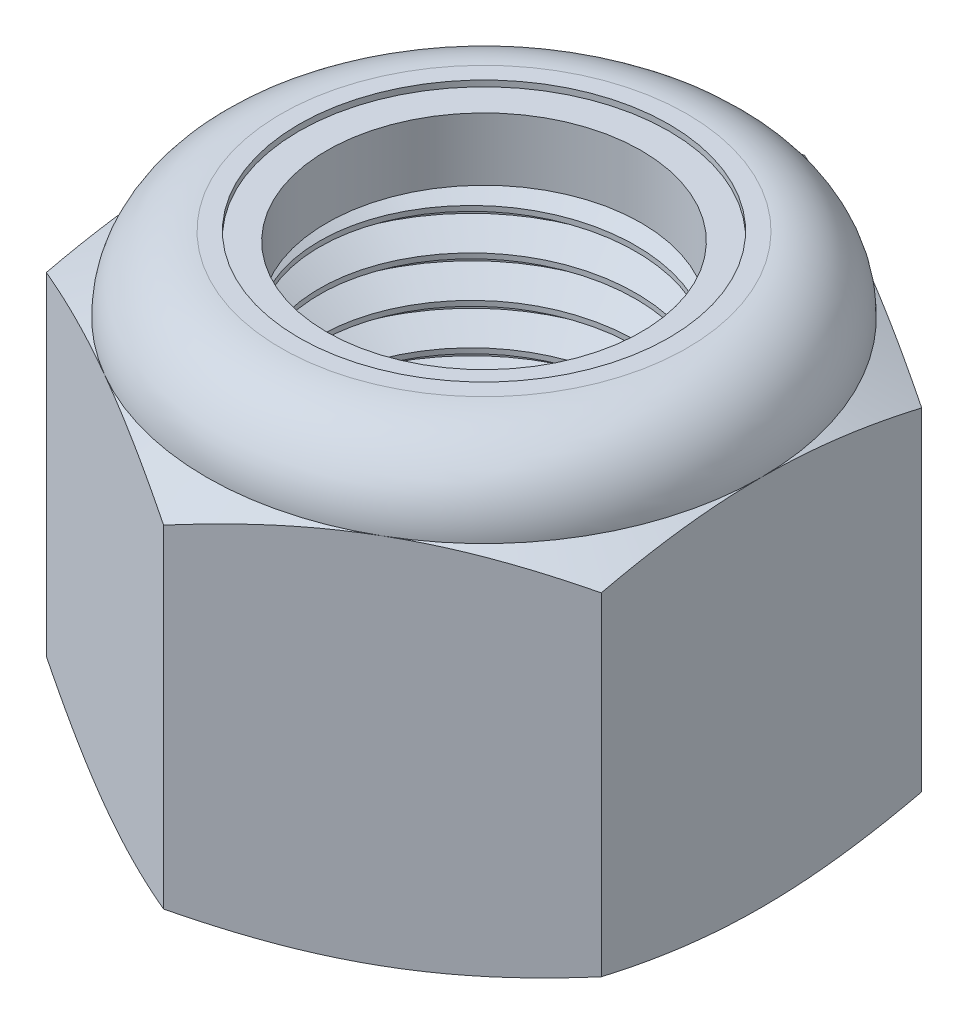
SolidWorks part; units mm, degrees
note: '?' marks a value the reader was unsure of.
ref_plane "Front" through (0, 0, 0) normal (0, 0, 1) x (1, 0, 0)
ref_plane "Top" through (0, 0, 0) normal (0, 1, 0) x (1, 0, 0)
ref_plane "Right" through (0, 0, 0) normal (1, 0, 0) x (0, 0, -1)
sketch "Sketch8" plane through (0, 0, 0) normal (1, 0, 0) x (0, 0, -1)
  line L0 (0, 0) -> (0, 11.5094) construction
  line L1 (7.1437, 0) -> (-7.1437, 0) construction
  line L2 (-4.7625, 11.5094) -> (4.7625, 11.5094) construction
  line L3 (4.7625, 11.5094) -> (4.7625, 10.451) construction
sketch "Sketch1" plane through (0, 0, 0) normal (0, 1, 0) x (1, 0, 0)
  line L1 (0, 8.2489) -> (-7.1438, 4.1244)
  line L2 (-7.1438, 4.1244) -> (-7.1437, -4.1244)
  line L3 (-7.1437, -4.1244) -> (0, -8.2489)
  line L4 (0, -8.2489) -> (7.1438, -4.1244)
  line L5 (7.1438, -4.1244) -> (7.1438, 4.1244)
  line L6 (7.1438, 4.1244) -> (0, 8.2489)
  circle A0 centre (0, 0) radius 7.1438 construction
  circle A1 centre (0, 0) radius 4.7625
extrude "Extrude1" add sketch "Sketch1" along normal up to vertex (11.5094 mm away) up to point (0, 11.5094, 0)
sketch "Sketch5" plane through (0, 0, 0) normal (1, 0, 0) x (0, 0, -1)
  line L0 (0, 0) -> (7.1437, 0)
  line L1 (7.1437, 0) -> (8.2489, 0.5153)
  line L2 (8.2489, 0.5153) -> (8.2489, 9.0758)
  line L3 (8.2489, 9.0758) -> (7.1437, 9.5911)
  line L4 (5.2255, 11.5094) -> (5.2255, 12.7794)
  line L5 (5.2255, 12.7794) -> (9.5189, 12.7794)
  line L6 (9.5189, 12.7794) -> (9.5189, -1.27)
  line L7 (9.5189, -1.27) -> (0, -1.27)
  line L8 (0, -1.27) -> (0, 0)
  line L9 (7.1437, 9.5911) -> (7.1437, 0) construction
  line L12 (8.2489, 11.5094) -> (8.2489, 0) construction
  line L13 (8.2489, 5.7547) -> (9.5189, 5.7547) construction
  line L15 (0, 0) -> (0, 12.7794) construction
  line L18 (7.1437, 0) -> (-7.1437, 0) construction
  line L19 (4.1244, 11.5094) -> (8.2489, 11.5094) construction
  line L20 (0, 12.7794) -> (5.2255, 12.7794) construction
  line L21 (4.1244, 0) -> (8.2489, 0) construction
  arc A0 (7.1437, 9.5911) -> (5.2255, 11.5094) centre (5.2255, 9.5911) ccw
  dimension "D1" = 25
  dimension "D2" = 1.27
  dimension "D4" = 1.9182
revolve "Cut-Revolve3" cut sketch "Sketch5" angle 360 about L15
sketch "Sketch4" plane through (0, 0, 0) normal (1, 0, 0) x (0, 0, -1)
  line L0 (0, 9.5911) -> (5.2388, 9.5911)
  line L1 (5.2388, 9.5911) -> (0, 7.1483)
  line L3 (0, 2.4429) -> (5.2388, 0)
  line L4 (5.2388, 0) -> (0, 0)
  line L5 (0, 0) -> (0, 9.5911) construction
  line L10 (0, 0) -> (0, 11.5094) construction
  line L11 (0, 2.4429) -> (0, 0)
  line L12 (0, 9.5911) -> (0, 7.1483)
  line L13 (6.1867, 9.5911) -> (0, 9.5911) construction
  dimension "D1" = 25
  dimension "D2" = 10.4775
sketch "Sketch6" plane through (0, 0, 0) normal (1, 0, 0) x (0, 0, -1)
  line L0 (0, 9.5911) -> (6.9913, 9.5911)
  line L1 (5.2255, 11.357) -> (2.6128, 11.357)
  line L2 (0, 12.7794) -> (0, 9.5911)
  line L3 (2.6128, 12.7794) -> (0, 12.7794)
  line L4 (0, 12.7794) -> (5.2255, 12.7794) construction
  line L5 (0, 0) -> (0, 12.7794) construction
  line L6 (0, 12.7794) -> (0, 0) construction
  line L7 (2.6128, 11.357) -> (2.6128, 12.7794)
  line L8 (5.2255, 11.5094) -> (5.2255, 11.357) construction
  line L9 (2.6128, 11.357) -> (0, 11.357) construction
  line L10 (0, 11.357) -> (0, 7.1483) construction
  arc A0 (6.9913, 9.5911) -> (5.2255, 11.357) centre (5.2255, 9.5911) ccw
  arc A1 (7.1437, 9.5911) -> (5.2255, 11.5094) centre (5.2255, 9.5911) ccw construction
  dimension "D1" = 0.1524
revolve "Cut-Revolve4" cut sketch "Sketch6" angle 360 about L6
revolve "Cut-Revolve2" cut sketch "Sketch4" angle 360 about L5
sketch "Sketch7" plane through (0, 0, 0) normal (1, 0, 0) x (0, 0, -1)
  line L0 (4.0481, 9.6673) -> (6.9134, 9.6673)
  line L1 (5.2255, 11.2808) -> (4.0481, 11.2808)
  line L2 (4.0481, 11.2808) -> (4.0481, 9.6673)
  line L3 (4.0481, 9.6673) -> (0, 9.6673) construction
  line L4 (0, 9.6673) -> (0, 11.2808) construction
  line L5 (0, 11.2808) -> (4.0481, 11.2808) construction
  line L6 (4.0481, 9.6673) -> (4.0481, 9.5911) construction
  line L7 (0, 9.5911) -> (6.9913, 9.5911) construction
  line L8 (5.2255, 11.2808) -> (5.2255, 11.357) construction
  arc A0 (6.9134, 9.6673) -> (5.2255, 11.2808) centre (5.2255, 9.5911) ccw
  arc A2 (6.9913, 9.5911) -> (5.2255, 11.357) centre (5.2255, 9.5911) ccw construction
  dimension "D1" = 0.0762
  dimension "D2" = 8.0963
revolve "Revolve2" add sketch "Sketch7" angle 360 about L4
sketch "Sketch2" plane through (0, 0, 0) normal (1, 0, 0) x (0, 0, -1)
  line L0 (-4.7625, 0) -> (-4.7625, 9.5911) construction
  line L1 (0, 0) -> (4.7625, 0)
  line L2 (0, 0) -> (0, 9.5911)
  line L3 (0, 9.5911) -> (4.7625, 9.5911)
  line L4 (4.7625, 0) -> (4.7625, 9.5911)
  line L6 (6.1867, 9.5911) -> (7.1437, 9.5911) construction
  line L7 (0, -4.7625) -> (0, 0) construction
revolve "Revolve1" add sketch "Sketch2" angle 360 about L7
sketch "Sketch9" plane through (0, 0, 0) normal (1, 0, 0) x (0, 0, -1)
  line L0 (4.8771, 10.5833) -> (4.8771, 9.525) construction
  line L1 (4.8771, 9.525) -> (3.9605, 10.0542) construction
  line L2 (3.9605, 10.0542) -> (4.8771, 10.5833) construction
  line L3 (4.0751, 10.1203) -> (4.0751, 9.988) construction
  line L4 (4.7625, 10.5172) -> (4.7625, 9.5911) construction
  line L5 (3.9605, 10.0542) -> (4.0751, 10.0542) construction
  line L6 (4.7625, 10.0542) -> (4.8771, 10.0542) construction
  line L7 (4.8198, 10.0542) -> (4.8198, 10.5503) construction
  line L8 (4.8771, 9.525) -> (4.8198, 10.5503)
  line L9 (4.8198, 10.5503) -> (4.0751, 10.1203)
  line L10 (4.0751, 10.1203) -> (4.0751, 9.988)
  line L11 (4.0751, 9.988) -> (4.8771, 9.525)
  dimension "D1" = 1.0583
  dimension "D2" = 0.1323
sketch "Sketch10" plane through (0, 9.5911, 0) normal (0, 1, 0) x (1, 0, 0)
  circle A1 centre (0, 0) radius 4.7625
  circle A2 centre (0, 0) radius 4.7625
  dimension "D1" = 0
curve "Helix/Spiral1" pitch 1.0583 height 12.5677 turns 11.875
sweep "Cut-Sweep1" cut profiles "Sketch9" path "Helix/Spiral1" align with end faces yes
sketch "Sketch11" plane through (0, 0, 0) normal (1, 0, 0) x (0, 0, -1)
  line L0 (0, 0) -> (0, 11.5094) construction
  line L1 (7.1437, 0) -> (-7.1437, 0) construction
  line L4 (0, 11.5094) -> (0, 0) construction
  line L5 (0, 5.7547) -> (4.7625, 5.7547) construction
  line L6 (0, 0) -> (5.2388, 0)
  line L7 (0, 2.4429) -> (0, 0)
  line L8 (5.2388, 0) -> (0, 2.4429)
  dimension "D1" = 10.4775
  dimension "D2" = 25
revolve "Revolve3" add sketch "Sketch11" angle 360 about L4
sketch "Sketch12" plane through (0, 0, 0) normal (1, 0, 0) x (0, 0, -1)
  line L0 (5.2388, 9.5911) -> (0, 9.5911)
  line L1 (0, 9.5911) -> (0, 0)
  line L2 (0, 0) -> (5.2388, 0)
  line L3 (7.1437, 0) -> (-7.1437, 0) construction
  line L4 (5.2388, 0) -> (5.2388, 9.5911)
  line L5 (-5.2388, 0) -> (5.2388, 0) construction
revolve "Revolve4" add sketch "Sketch12" angle 360 about L0
combine bodies "Combine1" operation type subtract main body 136 bodies to subtract 133
ref_plane "Contact Plane 1" through (0, 0, 0) normal (0, -1, 0) x (1, 0, 0)
ref_axis "Center Axis 1" through (0, -2.1015, 0) along (0, 1, 0)?
equation "\"D4@Sketch5\"=\"Height@Sketch8\"/6"
equation "\"D1@Sketch9\"=\"Thread Pitch@Sketch8\""
equation "\"D2@Sketch9\"=\"Thread Pitch@Sketch8\"/8"
equation "\"D4@Helix/Spiral1\"=\"Thread Pitch@Sketch8\""
equation "\"D3@Helix/Spiral1\"=\"Thread Pitch@Sketch8\"+\"Height@Sketch8\""
equation "\"D2@Sketch4\"=\"Thread Dia@Sketch8\"*1.1"
equation "\"D1@Sketch11\"=\"Thread Dia@Sketch8\"*1.1"
equation "\"D2@Sketch7\"=\"Thread Dia@Sketch8\"*.85"
